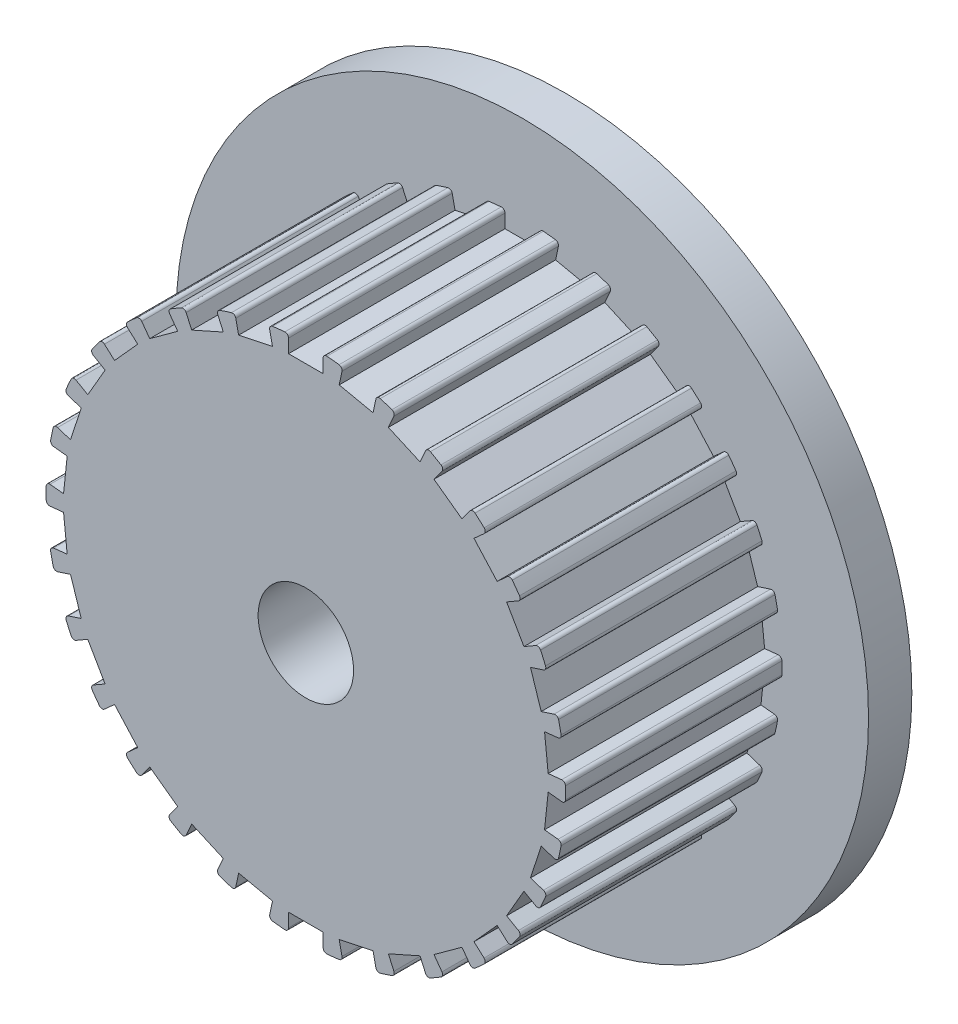
SolidWorks part; units mm, degrees
ref_plane "Front Plane" through (0, 0, 0) normal (0, 0, 1) x (1, 0, 0)
ref_plane "Top Plane" through (0, 0, 0) normal (0, 1, 0) x (1, 0, 0)
ref_plane "Right Plane" through (0, 0, 0) normal (1, 0, 0) x (0, 0, -1)
sketch "Sketch1" plane through (0, 0, 0) normal (0, 0, 1) x (1, 0, 0)
  circle A0 centre (0, 0) radius 12.7
  dimension "D1" = 25.4
extrude "Boss-Extrude1" add sketch "Sketch1" along normal blind 1.5875
sketch "Sketch2" plane through (0, 0, 1.5875) normal (0, 0, 1) x (1, 0, 0)
  circle A0 centre (0, 0) radius 9.525
  dimension "D1" = 19.05
extrude "Boss-Extrude2" add sketch "Sketch2" along normal blind 7.9375
sketch "Sketch3" plane through (0, 0, 9.525) normal (0, 0, 1) x (1, 0, 0)
  circle A0 centre (0, 0) radius 1.75
  dimension "D1" = 3.5
extrude "Cut-Extrude1" cut sketch "Sketch3" against normal through all
sketch "Sketch4" plane through (0, 0, 9.525) normal (0, 0, 1) x (1, 0, 0)
  line L0 (0, 8.8688) -> (0, 9.525) construction
  line L6 (-0.635, 9.5038) -> (0.635, 9.5038)
  line L7 (-0.635, 9.5038) -> (-0.635, 10.1388)
  line L8 (-0.635, 10.1388) -> (0.635, 10.1388)
  line L9 (0.635, 9.5038) -> (0.635, 10.1388)
  line L10 (-0.635, 9.5038) -> (0.635, 9.5038)
  line L11 (-0.635, 9.5038) -> (-0.635, 8.8688)
  line L12 (-0.635, 8.8688) -> (0.635, 8.8688)
  line L13 (0.635, 9.5038) -> (0.635, 8.8688)
  circle A0 centre (0, 0) radius 9.525 construction
  circle A5 centre (0, 0) radius 9.525 construction
  point P13 (0, 9.4966)
  dimension "D1" = 1.27
  dimension "D2" = 0.635
  dimension "D4" = 0.635
extrude "Cut-Extrude2" cut sketch "Sketch4" against normal up to surface (7.9375 mm away) contours L12 L13 L10 L11 | L7 L6 L9 L8 up to face at (9.525, 0, 1.5875)
fillet "Fillet2" radius 0.127 2 edges at (0.635, 9.5038, 5.5563) (-0.635, 9.5038, 5.5563)
pattern_circular "CirPattern1" count 30 over 360 about axis through (0, 0, 1.5875) along (0, 0, 1) of "Cut-Extrude2", "Fillet2"
